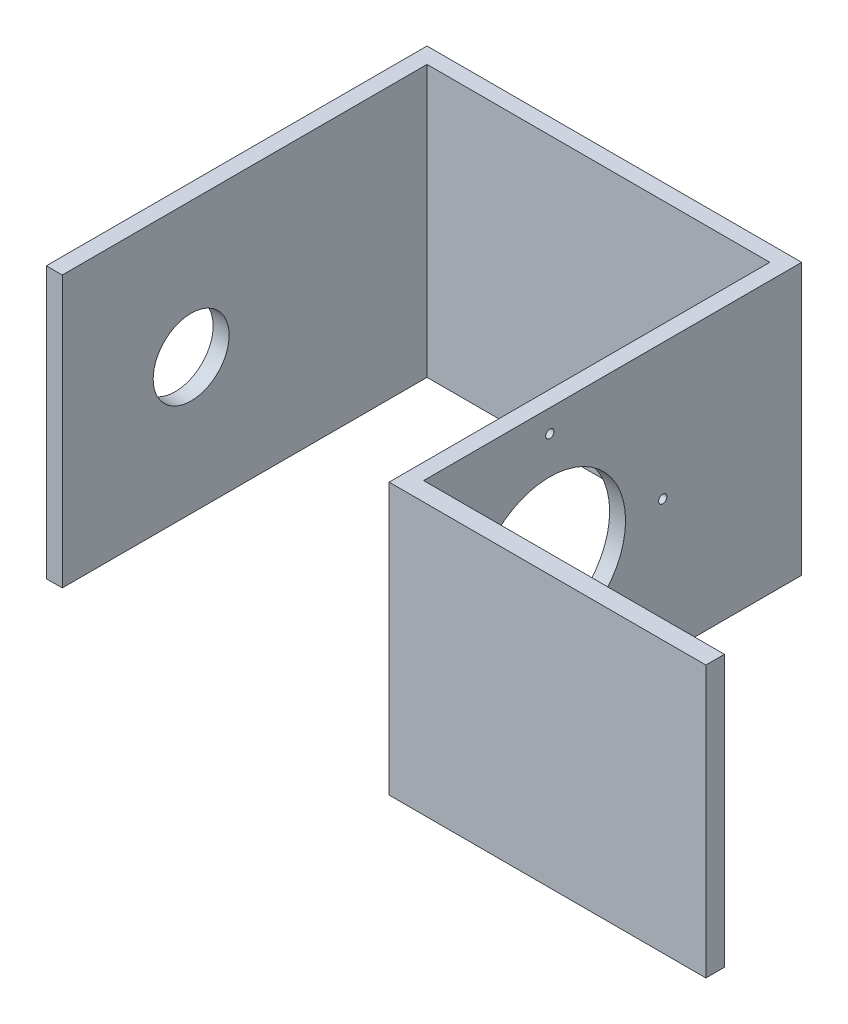
SolidWorks part; units mm, degrees
ref_plane "Front Plane" through (0, 0, 0) normal (0, 0, 1) x (1, 0, 0)
ref_plane "Top Plane" through (0, 0, 0) normal (0, 1, 0) x (1, 0, 0)
ref_plane "Right Plane" through (0, 0, 0) normal (1, 0, 0) x (0, 0, -1)
sketch "Sketch1" plane through (0, 0, 0) normal (0, 1, 0) x (1, 0, 0)
  line L0 (-47.5, -29.9135) -> (47.5, -29.9135) construction
  line L1 (-47.5, 56.6115) -> (47.5, 56.6115) construction
  line L2 (-47.5, 56.6115) -> (-47.5, -56.6115) construction
  line L3 (-47.5, -56.6115) -> (47.5, -56.6115) construction
  line L4 (47.5, 56.6115) -> (47.5, -56.6115) construction
  line L5 (-47.5, 56.6115) -> (47.5, -56.6115) construction
  line L6 (-47.5, -56.6115) -> (47.5, 56.6115) construction
  line L7 (-47.5, -23.9135) -> (47.5, -23.9135) construction
  line L8 (-47.5, 23.5865) -> (47.5, 23.5865) construction
  line L9 (47.5, 27.5865) -> (-47.5, 27.5865) construction
  line L10 (97.198, 47.5) -> (97.198, -47.5) construction
  line L11 (183.723, 47.5) -> (183.723, -47.5) construction
  line L12 (183.723, 47.5) -> (70.5, 47.5) construction
  line L13 (70.5, 47.5) -> (70.5, -47.5) construction
  line L14 (183.723, -47.5) -> (70.5, -47.5) construction
  line L15 (183.723, 47.5) -> (70.5, -47.5) construction
  line L16 (70.5, 47.5) -> (183.723, -47.5) construction
  line L17 (103.198, 47.5) -> (103.198, -47.5) construction
  line L18 (150.698, 47.5) -> (150.698, -47.5) construction
  line L19 (154.698, -47.5) -> (154.698, 47.5) construction
  line L20 (64.5, 88.7731) -> (64.5, -54.5) construction
  line L21 (47.5, -56.6115) -> (-248.4804, -56.6115) construction
  line L22 (47.5, -56.6115) -> (47.5, -62.6115) construction
  line L23 (47.5, -62.6115) -> (-248.4804, -62.6115) construction
  line L24 (-248.4804, -56.6115) -> (-248.4804, -62.6115) construction
  line L25 (64.5, -54.5) -> (327.1082, -54.5) construction
  line L26 (70.5, 94.7731) -> (70.5, -48.5) construction
  line L27 (70.5, -48.5) -> (327.1082, -48.5) construction
  line L28 (70.5, -48.5) -> (70.5, -54.5) construction
  line L29 (70.5, -48.5) -> (64.5, -48.5) construction
  line L30 (47.5, -56.6115) -> (47.5, -62.6115) construction
  line L31 (48.5, 17.5865) -> (48.5, -30) construction
  line L32 (48.5, -30) -> (54.5, -30) construction
  line L33 (54.5, -30) -> (54.5, 23.5865) construction
  line L34 (0, 0) -> (0, 56.6115) construction
  line L35 (-48.5, -30) -> (-54.5, -30) construction
  line L36 (-54.5, -30) -> (-54.5, 23.5865) construction
  line L37 (-48.5, 17.5865) -> (-48.5, -30) construction
  line L38 (54.5, 23.5865) -> (-54.5, 23.5865) construction
  line L39 (-48.5, 17.5865) -> (48.5, 17.5865) construction
  line L40 (48.5, 17.5865) -> (48.5, 23.5865) construction
  line L41 (70.5, 94.7731) -> (-59.952, 94.7731) construction
  line L42 (64.5, 88.7731) -> (-64.5, 88.7731) construction
  line L43 (-64.5, 88.7731) -> (-64.5, -48.5) construction
  line L44 (-64.5, -48.5) -> (-70.5, -48.5) construction
  line L45 (-70.5, -48.5) -> (-70.5, 98.5172) construction
  line L46 (-196.6321, -56.6115) -> (-196.6321, 23.9185) construction
  line L51 (-196.6321, -62.6115) -> (-101.6321, -62.6115) construction
  line L52 (-196.6321, -62.6115) -> (-196.6321, -89.3115) construction
  line L53 (-196.6321, -89.3115) -> (-101.6321, -89.3115) construction
  line L54 (-101.6321, -62.6115) -> (-101.6321, -89.3115) construction
  line L55 (-196.6321, 23.9185) -> (-101.6321, 23.9185) construction
  line L56 (-101.6321, 23.9185) -> (-101.6321, -56.6115) construction
  line L57 (-54.5, -23.9135) -> (-64.5, -23.9135) construction
  line L58 (54.5, -23.9135) -> (64.5, -23.9135) construction
  line L59 (64.5, 88.7731) -> (64.5, 94.7731) construction
  point P0 (0, 0)
  point P17 (127.1115, 0)
  dimension "D1" = 113.223
  dimension "D2" = 95
  dimension "D3" = 6
  dimension "D4" = 26.698
  dimension "D5" = 4
  dimension "D6" = 57.5
  dimension "D7" = 29.025
  dimension "D8" = 6
  dimension "D9" = 95
  dimension "D10" = 6
  dimension "D11" = 26.698
  dimension "D12" = 4
  dimension "D13" = 29.025
  dimension "D14" = 57.5
  dimension "D15" = 30
  dimension "D16" = 1
  dimension "D17" = 1
  dimension "D18" = 10
  dimension "D19" = 26.7
  dimension "D20" = 80.53
sketch "Sketch2" plane through (0, 0, 0) normal (0, 0, 1) x (1, 0, 0)
  line L0 (-47.5, 0) -> (47.5, 0) construction
  line L1 (-47.5, -50) -> (47.5, -50) construction
  line L2 (-47.5, -50) -> (-47.5, 50) construction
  line L3 (-47.5, 50) -> (47.5, 50) construction
  line L4 (47.5, -50) -> (47.5, 50) construction
  line L5 (-47.5, -50) -> (47.5, 50) construction
  line L6 (-47.5, 50) -> (47.5, -50) construction
  line L11 (0, 0) -> (0, 22.5) construction
  line L12 (-196.6321, 0) -> (-101.6321, 0) construction
  line L13 (-196.6321, 0) -> (-101.6321, 0) construction
  line L14 (0, 27.5) -> (-229.1321, 27.5)
  line L15 (-229.1321, 27.5) -> (-229.1321, -27.5)
  line L16 (-229.1321, -27.5) -> (0, -27.5)
  circle A0 centre (0, 0) radius 22.5 construction
  circle A1 centre (0, 22.5) radius 1.5635
  circle A2 centre (22.5, 0) radius 1.5635
  circle A3 centre (0, -22.5) radius 1.5635
  circle A4 centre (-22.5, 0) radius 1.5635
  circle A5 centre (-171.6321, 0) radius 1.5635
  circle A6 centre (-149.1321, 0) radius 22.5 construction
  circle A7 centre (-149.1321, 22.5) radius 1.5635
  circle A8 centre (-126.6321, 0) radius 1.5635
  circle A9 centre (-149.1321, -22.5) radius 1.5635
  arc A10 (0, 27.5) -> (0, -27.5) centre (0, 0) cw
  point P0 (0, 0)
  point P14 (0, 0)
  point P15 (0, 0)
  point P18 (0, 0)
  point P21 (0, 0)
  point P24 (0, 0)
  point P39 (-47.5, 51)
  point P40 (-47.5, -51)
  point P41 (0, 0)
  point P42 (0, 0)
  dimension "D3" = 45
  dimension "D4" = 3.127
  dimension "D7" = 5
  dimension "D1" = 100
  dimension "D2" = 95
  dimension "D8" = 80
  dimension "D9" = 1
  dimension "D6" = 2
  dimension "D5" = 4
extrude "Boss-Extrude1" [suppressed] add sketch "Sketch2" along normal up to vertex from vertex
sketch "Sketch3" plane through (0, 0, 0) normal (0, 1, 0) x (1, 0, 0)
  line L0 (-48.5, -30) -> (-54.5, -30) construction
  line L1 (-48.5, 17.5865) -> (-48.5, -30) construction
  line L2 (-54.5, -30) -> (-54.5, 23.5865) construction
  line L3 (-48.5, 17.5865) -> (48.5, 17.5865) construction
  line L4 (54.5, 23.5865) -> (-54.5, 23.5865) construction
  line L5 (54.5, -30) -> (54.5, 23.5865) construction
  line L6 (48.5, 17.5865) -> (48.5, -30) construction
  line L7 (48.5, -30) -> (54.5, -30) construction
  line L8 (-48.5, -30) -> (-54.5, -30)
  line L9 (-48.5, 17.5865) -> (-48.5, -30)
  line L10 (-54.5, -30) -> (-54.5, 23.5865)
  line L11 (-48.5, 17.5865) -> (48.5, 17.5865)
  line L12 (54.5, 23.5865) -> (-54.5, 23.5865)
  line L13 (54.5, -30) -> (54.5, 23.5865)
  line L14 (48.5, 17.5865) -> (48.5, -30)
  line L15 (48.5, -30) -> (54.5, -30)
extrude "Boss-Extrude2" [suppressed] add sketch "Sketch3" along normal up to vertex and the other way up to vertex
sketch "Sketch4" [suppressed] plane through (0, 0, -17.5865) normal (0, 0, 1) x (1, 0, 0)
  line L1 (30, -45) -> (-30, -45) construction
  line L2 (30, -45) -> (30, 45) construction
  line L3 (30, 45) -> (-30, 45) construction
  line L4 (-30, -45) -> (-30, 45) construction
  line L5 (30, -45) -> (-30, 45) construction
  line L6 (30, 45) -> (-30, -45) construction
  circle A0 centre (0, 0) radius 46.25
  circle A1 centre (-30, 45) radius 2.25
  circle A2 centre (30, 45) radius 2.25
  circle A3 centre (30, -45) radius 2.25
  circle A4 centre (-30, -45) radius 2.25
  dimension "D1" = 92.5
  dimension "D4" = 4.5
  dimension "D2" = 90
  dimension "D3" = 60
extrude "Cut-Extrude1" [suppressed] cut sketch "Sketch4" against normal through all
sketch "Sketch5" [suppressed] plane through (54.5, 0, 0) normal (1, 0, 0) x (0, 0, -1)
  circle A0 centre (0, 0) radius 14.2875
  point P0 (0, 0)
  dimension "D1" = 28.575
extrude "Cut-Extrude2" [suppressed] cut sketch "Sketch5" against normal through all
sketch "Sketch6" plane through (0, 0, 0) normal (0, 1, 0) x (1, 0, 0)
  line L0 (70.5, 94.7731) -> (70.5, -48.5) construction
  line L1 (70.5, 47.5) -> (70.5, -47.5) construction
  line L2 (183.723, -47.5) -> (70.5, -47.5) construction
  line L3 (64.5, -54.5) -> (327.1082, -54.5) construction
  line L4 (64.5, 88.7731) -> (64.5, -54.5) construction
  line L5 (64.5, 88.7731) -> (-64.5, 88.7731) construction
  line L6 (-70.5, -48.5) -> (-70.5, 98.5172) construction
  line L7 (-64.5, -48.5) -> (-70.5, -48.5) construction
  line L8 (-64.5, 88.7731) -> (-64.5, -48.5) construction
  line L9 (70.5, 94.7731) -> (70.5, -47.5)
  line L10 (70.5, 47.5) -> (70.5, -47.5)
  line L11 (183.723, -47.5) -> (70.5, -47.5)
  line L12 (64.5, -54.5) -> (183.723, -54.5)
  line L13 (64.5, 88.7731) -> (64.5, -54.5)
  line L14 (64.5, 88.7731) -> (-64.5, 88.7731)
  line L15 (-70.5, -48.5) -> (-70.5, 94.7731)
  line L16 (-64.5, -48.5) -> (-70.5, -48.5)
  line L17 (-64.5, 88.7731) -> (-64.5, -48.5)
  line L18 (70.5, 94.7731) -> (-70.5, 94.7731)
  line L19 (183.723, -47.5) -> (183.723, -54.5)
  point P12 (184.1045, -54.5)
  point P15 (0, 0)
  point P18 (-70.5, 94.6239)
extrude "Boss-Extrude3" add sketch "Sketch6" along normal up to vertex (51 mm away) and the other way up to vertex (51 mm away) contours L19 L11 L9 L18 L15 L16 L17 L14 L13 L12 region at (67.5519, 0, -71.1365) up to point (-47.5, 51, 0) other way up to point (-47.5, -51, 0)
sketch "Sketch7" plane through (70.5, 0, 0) normal (1, 0, 0) x (0, 0, -1)
  line L0 (47.5, 0) -> (-47.5, 0) construction
  circle A0 centre (0, 0) radius 42.5 construction
  circle A1 centre (0, 42.5) radius 1.5635
  circle A2 centre (42.5, 0) radius 1.5635
  circle A3 centre (0, -42.5) radius 1.5635
  circle A4 centre (-42.5, 0) radius 1.5635
  circle A5 centre (0, 0) radius 28.5
  point P15 (0, 0)
  dimension "D1" = 85
  dimension "D2" = 3.127
  dimension "D4" = 57
  dimension "D3" = 4
extrude "Cut-Extrude3" cut sketch "Sketch7" against normal up to next
sketch "Sketch8" plane through (-70.5, 0, 0) normal (-1, 0, 0) x (0, 0, 1)
  circle A0 centre (0, 0) radius 14.2875
  dimension "D1" = 28.575
extrude "Cut-Extrude4" cut sketch "Sketch8" against normal up to next
